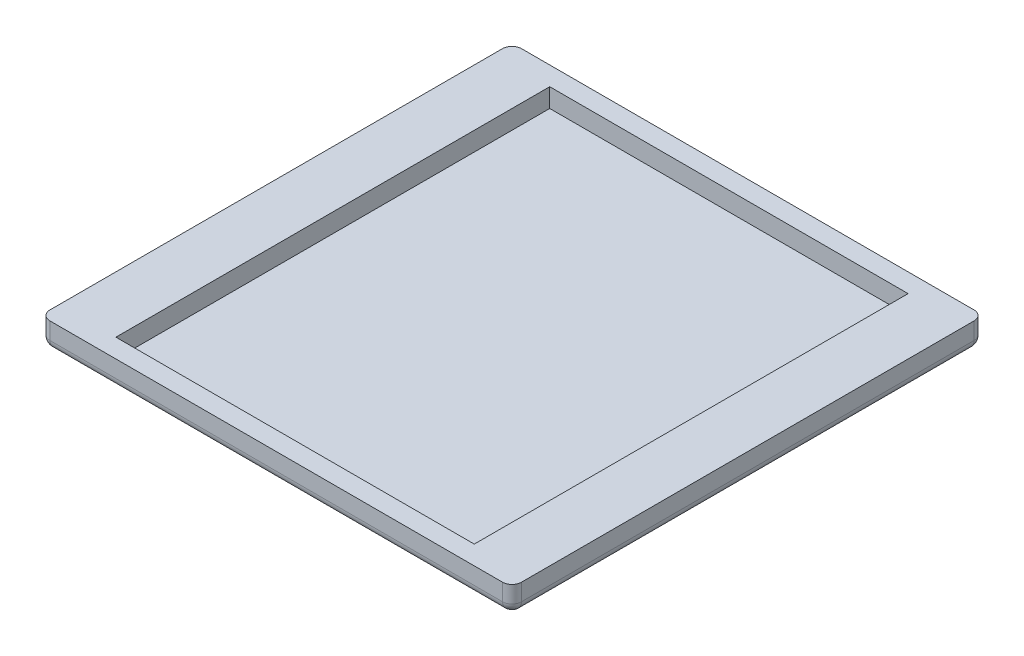
SolidWorks part; units mm, degrees
ref_plane "Front Plane" through (0, 0, 0) normal (0, 0, 1) x (1, 0, 0)
ref_plane "Top Plane" through (0, 0, 0) normal (0, 1, 0) x (1, 0, 0)
ref_plane "Right Plane" through (0, 0, 0) normal (1, 0, 0) x (0, 0, -1)
sketch "Sketch1" plane through (0, 0, 0) normal (0, 1, 0) x (1, 0, 0)
  line L1 (-125, -125) -> (125, -125)
  line L2 (-125, -125) -> (-125, 125)
  line L3 (-125, 125) -> (125, 125)
  line L4 (125, -125) -> (125, 125)
  line L5 (-125, -125) -> (125, 125) construction
  line L6 (-125, 125) -> (125, -125) construction
  point P0 (0, 0)
  dimension "D1" = 250
  dimension "D2" = 250
extrude "Base" add sketch "Sketch1" along normal blind 14
sketch "Sketch3" plane through (0, 14, 0) normal (0, 1, 0) x (1, 0, 0)
  line L0 (-95, 115) -> (-95, -115)
  line L1 (-95, 115) -> (95, 115)
  line L3 (-95, -115) -> (95, -115)
  line L5 (95, 115) -> (95, -115)
  line L6 (125, 125) -> (-125, 125) construction
  line L7 (-125, 125) -> (-125, -125) construction
  line L8 (125, -125) -> (125, 125) construction
  line L12 (-125, -125) -> (125, -125) construction
  point P0 (0, 0)
  dimension "D3" = 10
  dimension "D5" = 10
  dimension "D1" = 30
  dimension "D2" = 30
extrude "Cut-Extrude1" cut sketch "Sketch3" against normal blind 10
fillet "Fillet1" radius 5 4 edges at (0, 0, -125) (-125, 0, 0) (0, 0, 125) (125, 0, 0)
fillet "Fillet2" radius 5 8 edges at (-123.5355, 1.4645, 123.5355) (-125, 9.5, 125) (123.5355, 1.4645, -123.5355) (123.5355, 1.4645, 123.5355) (-123.5355, 1.4645, -123.5355) (125, 9.5, -125) (125, 9.5, 125) (-125, 9.5, -125)
equation "\"Width\"= 250"
equation "\"D1@Sketch1\"=\"Width\""
equation "\"Depth\" = 250"
equation "\"D2@Sketch1\"=\"Depth\""
equation "\"height\"= 14"
equation "\"D1@Base\"=\"height\""
equation "\"r1\"=5"
equation "\"D1@Fillet2\"=\"r1\""
equation "\"D1@Fillet1\"=\"r1\""
equation "\"cut1\"= 10"
equation "\"D1@Cut-Extrude1\"=\"cut1\""
equation "\"border1\"=10"
equation "\"D3@Sketch3\"=\"border1\""
equation "\"D5@Sketch3\"=\"border1\""
equation "\"rail_mount_width\"=130"
equation "\"border2\"= 30"
equation "\"D1@Sketch3\"=\"border2\""
equation "\"D2@Sketch3\"=\"border2\""
